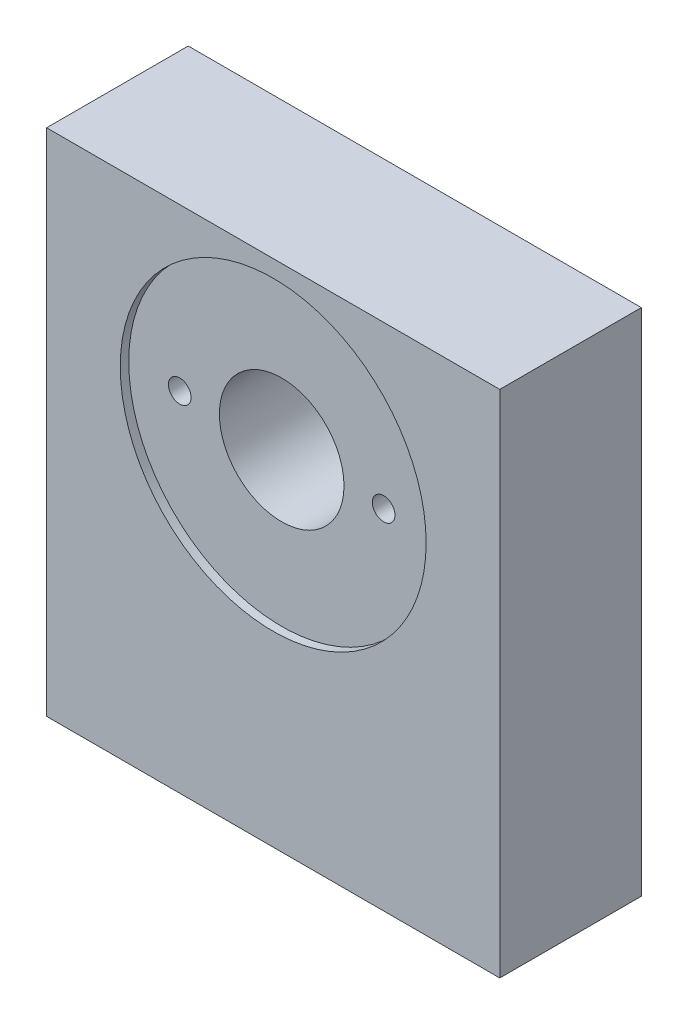
SolidWorks part; units mm, degrees
ref_plane "前视基准面" through (0, 0, 0) normal (0, 0, 1) x (1, 0, 0)
ref_plane "上视基准面" through (0, 0, 0) normal (0, 1, 0) x (1, 0, 0)
ref_plane "右视基准面" through (0, 0, 0) normal (1, 0, 0) x (0, 0, -1)
sketch "草图5" plane through (0, 0, 0) normal (0, 1, 0) x (1, 0, 0)
  line L1 (-40, -12.5) -> (40, -12.5)
  line L2 (-40, -12.5) -> (-40, 12.5)
  line L3 (-40, 12.5) -> (40, 12.5)
  line L4 (40, -12.5) -> (40, 12.5)
  line L5 (-40, -12.5) -> (40, 12.5) construction
  line L6 (-40, 12.5) -> (40, -12.5) construction
  point P0 (0, 0)
  dimension "D1" = 25
  dimension "D2" = 80
extrude "凸台-拉伸4" add sketch "草图5" along normal blind 90 separate body
sketch "草图6" plane through (0, 0, 12.5) normal (0, 0, 1) x (1, 0, 0)
  line L0 (0, 60) -> (0, 0) construction
  circle A0 centre (0, 60) radius 27
  circle A1 centre (-18, 60) radius 2
  circle A2 centre (0, 60) radius 11
  circle A3 centre (18, 60) radius 2
  dimension "D1" = 54
  dimension "D3" = 22
  dimension "D4" = 4
  dimension "D2" = 60
extrude "切除-拉伸1" cut sketch "草图6" against normal blind 90 contours A1 | A2 | A3 region at (-18, 60, 12.5) region at (0, 60, 12.5) region at (18, 60, 12.5)
extrude "切除-拉伸2" cut sketch "草图6<3>" against normal blind 1.5
sketch "草图6<3>" plane through (0, 0, 12.5) normal (0, 0, 1) x (1, 0, 0) same geometry as "草图6"
